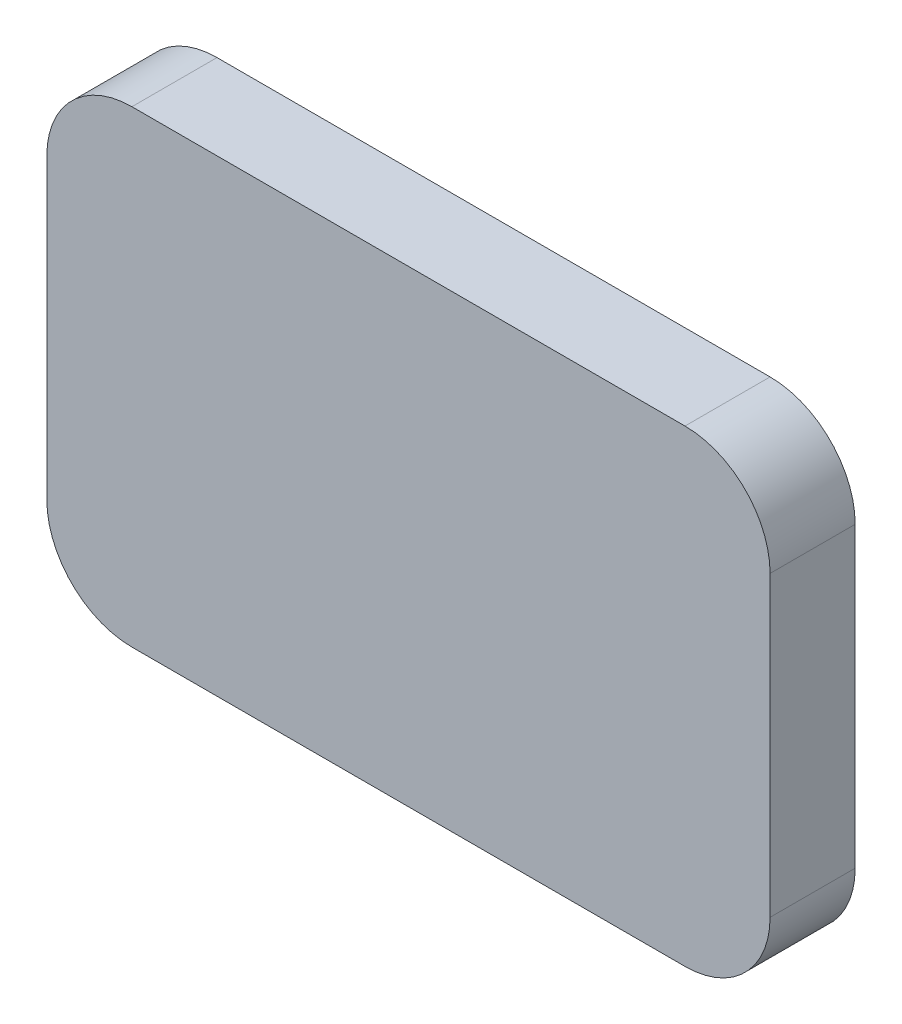
SolidWorks part; units mm, degrees
ref_plane "Front Plane" through (0, 0, 0) normal (0, 0, 1) x (1, 0, 0)
ref_plane "Top Plane" through (0, 0, 0) normal (0, 1, 0) x (1, 0, 0)
ref_plane "Right Plane" through (0, 0, 0) normal (1, 0, 0) x (0, 0, -1)
sketch "Sketch1" plane through (0, 0, 0) normal (0, 0, 1) x (1, 0, 0)
  line L1 (0, 0) -> (17, 0)
  line L2 (0, 0) -> (0, 11)
  line L3 (0, 11) -> (17, 11)
  line L4 (17, 0) -> (17, 11)
  line L5 (17, 7.25) -> (17, 4.9873)
  line L24 (17, 11) -> (-49983, 11) construction
  dimension "D1" = 11
  dimension "D2" = 17
extrude "Boss-Extrude2" add sketch "Sketch1" along normal blind 2 contours L1 L4 L3 L2 | L4 region at (8.5, 5.5, 0)
fillet "Fillet1" radius 2 4 edges at (0, 0, 1) (17, 0, 1) (17, 11, 1) (0, 11, 1)
